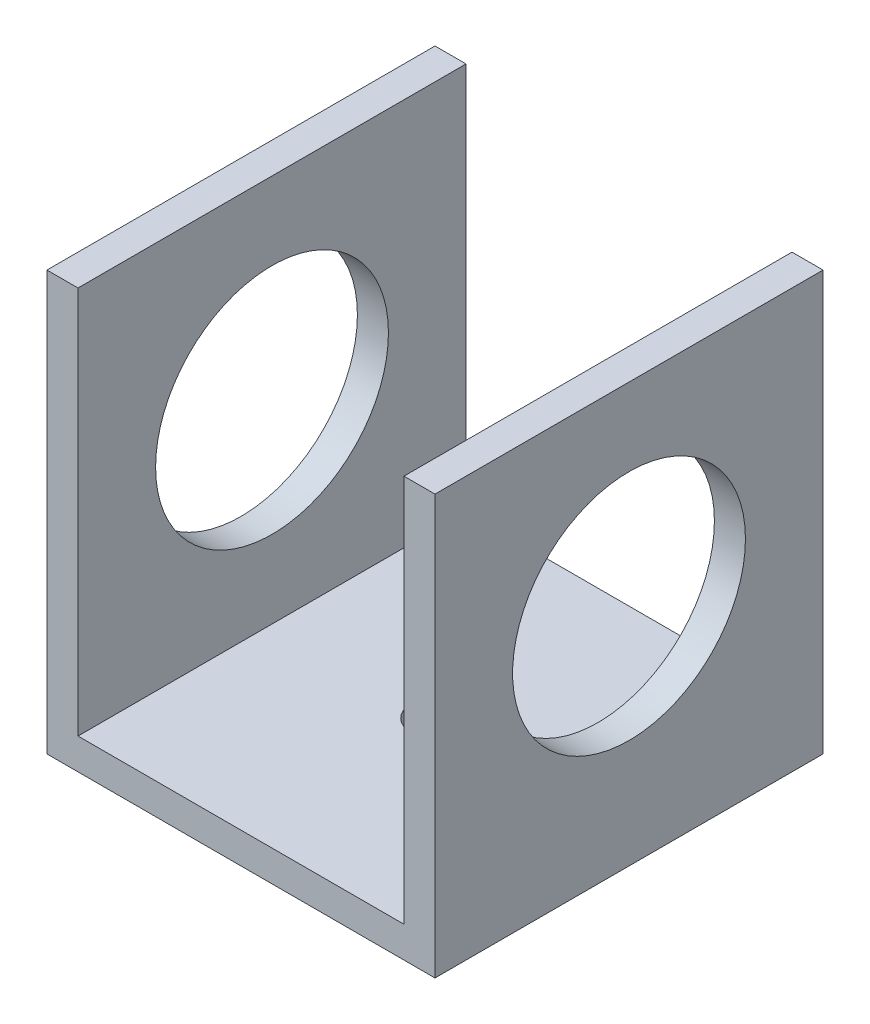
SolidWorks part; units mm, degrees
ref_plane "Front Plane" through (0, 0, 0) normal (0, 0, 1) x (1, 0, 0)
ref_plane "Top Plane" through (0, 0, 0) normal (0, 1, 0) x (1, 0, 0)
ref_plane "Right Plane" through (0, 0, 0) normal (1, 0, 0) x (0, 0, -1)
sketch "Sketch1" plane through (0, 0, 0) normal (0, 1, 0) x (1, 0, 0)
  line L1 (-25.4, -25.4) -> (25.4, -25.4)
  line L2 (-25.4, -25.4) -> (-25.4, 25.4)
  line L3 (-25.4, 25.4) -> (25.4, 25.4)
  line L4 (25.4, -25.4) -> (25.4, 25.4)
  line L5 (-25.4, -25.4) -> (25.4, 25.4) construction
  line L6 (-25.4, 25.4) -> (25.4, -25.4) construction
  circle A0 centre (0, 0) radius 3.175
  point P0 (0, 0)
  dimension "D3" = 6.35
  dimension "D1" = 50.8
  dimension "D2" = 50.8
extrude "Boss-Extrude1" add sketch "Sketch1" along normal blind 4.064
sketch "Sketch2" plane through (0, 4.064, 0) normal (0, 1, 0) x (1, 0, 0)
  line L0 (-25.4, -25.4) -> (25.4, -25.4) construction
  line L1 (-25.4, 25.4) -> (-21.336, 25.4)
  line L2 (-25.4, 25.4) -> (-25.4, -25.4)
  line L3 (-25.4, -25.4) -> (-21.336, -25.4)
  line L4 (-21.336, 25.4) -> (-21.336, -25.4)
  line L6 (25.4, 25.4) -> (21.336, 25.4)
  line L7 (25.4, 25.4) -> (25.4, -25.4)
  line L8 (25.4, -25.4) -> (21.336, -25.4)
  line L9 (21.336, 25.4) -> (21.336, -25.4)
  dimension "D1" = 4.064
  dimension "D2" = 4.064
extrude "Boss-Extrude2" add sketch "Sketch2" along normal blind 50.8
sketch "Sketch3" plane through (25.4, 0, 0) normal (1, 0, 0) x (0, 0, -1)
  line L0 (25.4, 54.864) -> (25.4, 0) construction
  line L1 (-25.4, 0) -> (25.4, 0) construction
  circle A0 centre (0, 29.464) radius 15.24
  dimension "D1" = 30.48
  dimension "D2" = 25.4
  dimension "D3" = 29.464
extrude "Cut-Extrude1" cut sketch "Sketch3" against normal through all
